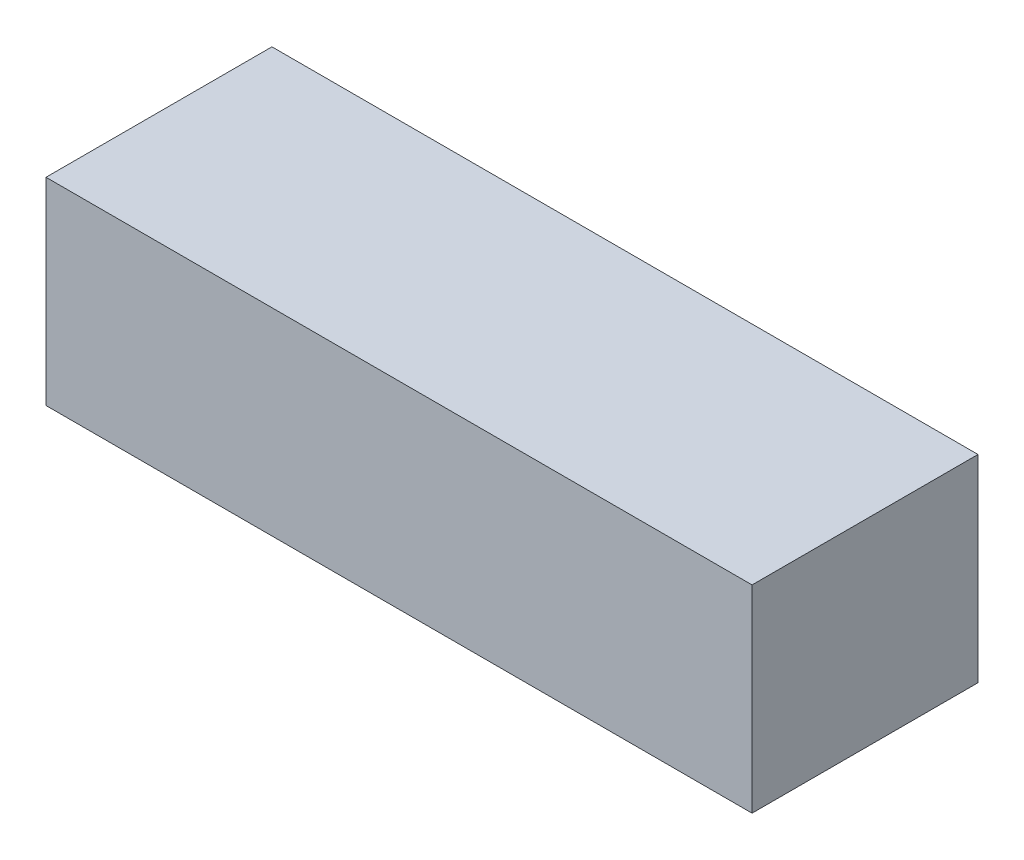
SolidWorks part; units mm, degrees
ref_plane "前视基准面" through (0, 0, 0) normal (0, 0, 1) x (1, 0, 0)
ref_plane "上视基准面" through (0, 0, 0) normal (0, 1, 0) x (1, 0, 0)
ref_plane "右视基准面" through (0, 0, 0) normal (1, 0, 0) x (0, 0, -1)
sketch "草图1" plane through (0, 0, 0) normal (0, 1, 0) x (1, 0, 0)
  line L1 (-12.5, 4) -> (12.5, 4)
  line L2 (-12.5, 4) -> (-12.5, -4)
  line L3 (-12.5, -4) -> (12.5, -4)
  line L4 (12.5, 4) -> (12.5, -4)
  line L5 (0, -4) -> (0, 4) construction
  line L6 (-12.5, 0) -> (12.5, 0) construction
  point P0 (0, 0)
  dimension "D1" = 25
  dimension "D2" = 8
extrude "凸台-拉伸1" add sketch "草图1" along normal blind 7 contours L3 L4 L1 L2
